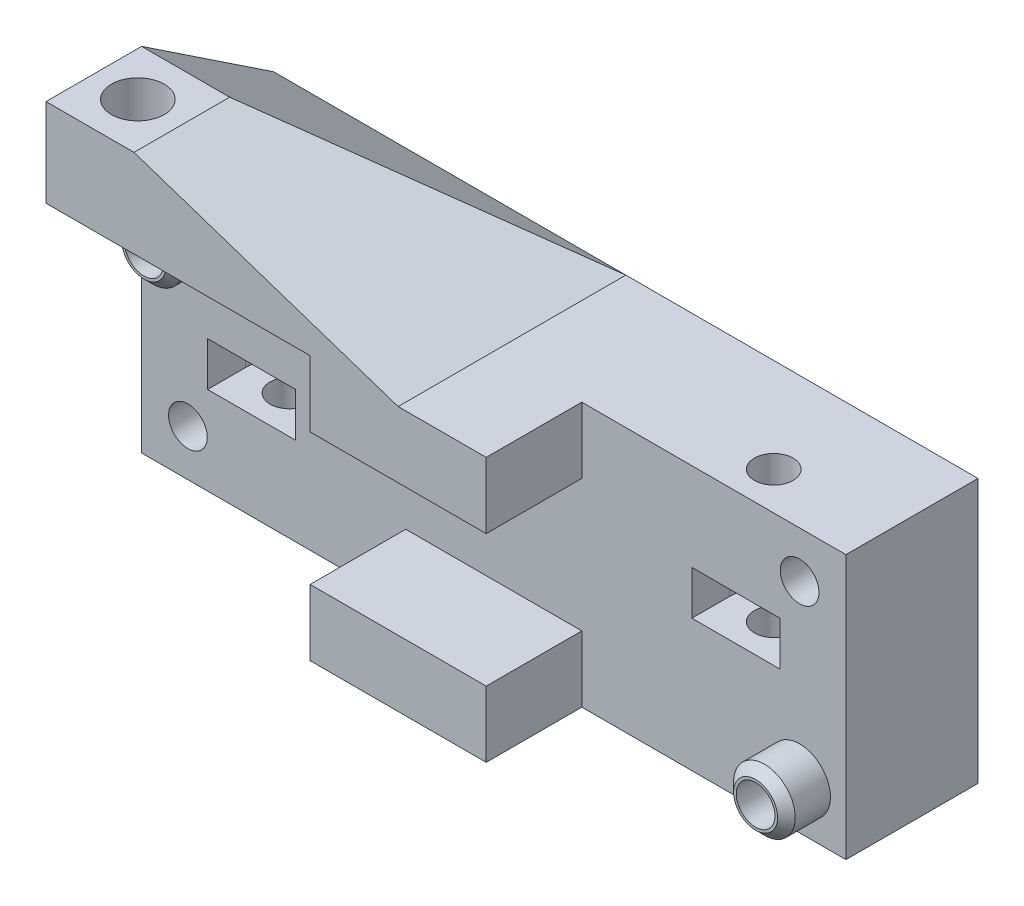
SolidWorks part; units mm, degrees
ref_plane "Front Plane" through (0, 0, 0) normal (0, 0, 1) x (1, 0, 0)
ref_plane "Top Plane" through (0, 0, 0) normal (0, 1, 0) x (1, 0, 0)
ref_plane "Right Plane" through (0, 0, 0) normal (1, 0, 0) x (0, 0, -1)
sketch "Sketch1" plane through (0, 0, 0) normal (0, 0, 1) x (1, 0, 0)
  line L1 (-25.4, 9.525) -> (25.4, 9.525)
  line L2 (-25.4, 9.525) -> (-25.4, -9.525)
  line L3 (-25.4, -9.525) -> (25.4, -9.525)
  line L4 (25.4, 9.525) -> (25.4, -9.525)
  line L5 (-25.4, 9.525) -> (25.4, -9.525) construction
  line L6 (-25.4, -9.525) -> (25.4, 9.525) construction
  point P0 (0, 0)
  dimension "D1" = 50.8
  dimension "D2" = 19.05
extrude "Boss-Extrude1" add sketch "Sketch1" along normal blind 9.525
sketch "Sketch11" plane through (0, 9.525, 0) normal (0, 1, 0) x (1, 0, 0)
  line L1 (-25.4, 0) -> (0, 0)
  line L2 (-25.4, 0) -> (-25.4, -16.4211)
  line L3 (-25.4, -16.4211) -> (0, -16.4211)
  line L4 (0, 0) -> (0, -16.4211)
  line L5 (-25.4, -25.9461) -> (-25.4, -16.4211) construction
  line L6 (12.6942, -16.4211) -> (0, -16.4211) construction
  dimension "D1" = 25.4
extrude "Boss-Extrude5" add sketch "Sketch11" along normal blind 6.35
sketch "Sketch2" plane through (0, 0, 9.525) normal (0, 0, 1) x (1, 0, 0)
  line L0 (-22.0599, -6.1849) -> (-22.0599, 6.1849) construction
  line L1 (-22.0599, 6.1849) -> (-25.4, 6.1849) construction
  line L2 (-25.4, 9.525) -> (-25.4, -9.525) construction
  line L3 (-22.0599, 6.1849) -> (-22.0599, 9.525) construction
  line L4 (25.4, 9.525) -> (0, 9.525) construction
  line L5 (0, -9.525) -> (0, 9.525) construction
  line L6 (25.4, 9.525) -> (0, 9.525) construction
  circle A0 centre (-22.0599, -6.1849) radius 1.397
  circle A1 centre (-22.0599, 6.1849) radius 1.397
  circle A2 centre (22.0599, -6.1849) radius 1.397
  circle A3 centre (22.0599, 6.1849) radius 1.397
  point P4 (-22.0599, 0)
  point P16 (0, 0)
  dimension "D1" = 2.794
  dimension "D2" = 2.794
  dimension "D3" = 12.3698
extrude "Cut-Extrude1" cut sketch "Sketch2" against normal through all
sketch "Sketch5" plane through (0, 9.525, 0) normal (0, 1, 0) x (1, 0, 0)
  line L0 (-25.4, -9.525) -> (-25.4, 0) construction
  line L1 (25.4, 0) -> (0, 0) construction
  line L2 (0, 0) -> (0, -9.525) construction
  line L4 (25.4, -9.525) -> (0, -9.525) construction
  circle A0 centre (-17.4625, -6.7945) radius 1.397
  circle A1 centre (17.4625, -6.7945) radius 1.397
  dimension "D1" = 7.9375
  dimension "D2" = 2.794
  dimension "D3" = 6.7945
extrude "Cut-Extrude3" cut sketch "Sketch5" against normal through all
sketch "Sketch3" plane through (0, 9.525, 0) normal (0, 1, 0) x (1, 0, 0)
  line L0 (-20.6375, -6.7945) -> (-20.6375, -9.525)
  line L1 (25.4, -9.525) -> (0, -9.525) construction
  line L2 (-14.2875, -6.7945) -> (-14.2875, -9.525)
  line L3 (-14.2875, -9.525) -> (-20.6375, -9.525)
  arc A0 (-14.2875, -6.7945) -> (-20.6375, -6.7945) centre (-17.4625, -6.7945) ccw
  circle A1 centre (-17.4625, -6.7945) radius 1.397 construction
  dimension "D1" = 3.175
extrude "Cut-Extrude2" cut sketch "Sketch3" against normal blind 3.175 from offset 9.525 offset against normal yes
sketch "Sketch6" plane through (0, 9.525, 0) normal (0, 1, 0) x (1, 0, 0)
  line L0 (14.2875, -6.7945) -> (14.2875, -9.525)
  line L1 (25.4, -9.525) -> (0, -9.525) construction
  line L2 (20.6375, -6.7945) -> (20.6375, -9.525)
  line L3 (14.2875, -9.525) -> (20.6375, -9.525)
  arc A0 (20.6375, -6.7945) -> (14.2875, -6.7945) centre (17.4625, -6.7945) ccw
  dimension "D1" = 6.35
extrude "Cut-Extrude4" cut sketch "Sketch6" against normal blind 3.175 from offset 6.35 offset against normal yes
sketch "Sketch7" plane through (0, 0, 9.525) normal (0, 0, 1) x (1, 0, 0)
  circle A0 centre (-22.0599, 6.1849) radius 2.2225
  circle A1 centre (-22.0599, 6.1849) radius 1.397
  circle A2 centre (22.0599, -6.1849) radius 2.2225
  circle A3 centre (22.0599, -6.1849) radius 1.397
  circle A5 centre (-22.0599, 6.1849) radius 1.397 construction
  circle A6 centre (22.0599, -6.1849) radius 1.397 construction
  dimension "D1" = 4.445
extrude "Boss-Extrude2" add sketch "Sketch7" along normal blind 3.175
chamfer "Chamfer1" distance 0.635 angle 45 2 edges at (-19.8374, 6.1849, 12.7) (24.2824, -6.1849, 12.7)
sketch "Sketch10" plane through (0, 0, 9.525) normal (0, 0, 1) x (1, 0, 0)
  line L0 (25.4, 9.525) -> (0, 9.525) construction
  line L1 (-6.35, 9.525) -> (6.35, 9.525)
  line L2 (-6.35, 9.525) -> (-6.35, 4.7625)
  line L3 (-6.35, 4.7625) -> (6.35, 4.7625)
  line L4 (6.35, 9.525) -> (6.35, 4.7625)
  line L5 (-25.4, -9.525) -> (25.4, -9.525) construction
  line L6 (-6.35, -9.525) -> (6.35, -9.525)
  line L7 (-6.35, -9.525) -> (-6.35, -4.7625)
  line L8 (-6.35, -4.7625) -> (6.35, -4.7625)
  line L9 (6.35, -9.525) -> (6.35, -4.7625)
  point P6 (0, 4.7625)
  point P14 (0, -4.7625)
  dimension "D1" = 12.7
  dimension "D2" = 4.7625
  dimension "D3" = 4.7625
  dimension "D4" = 12.7
extrude "Boss-Extrude4" add sketch "Sketch10" along normal blind 6.8961
chamfer "Chamfer2" distance 6.35 distance2 9.525 1 edges at (-12.7, 15.875, 0) first distance on face at (-20.6629, 6.1849, 0)
chamfer "Chamfer3" distance 6.35 distance2 19.05 1 edges at (0, 15.875, 12.9731) first distance on face at (0, 12.7, 10.5918)
sketch "Sketch12" plane through (0, 15.875, 0) normal (0, 1, 0) x (1, 0, 0)
  line L0 (-22.225, -12.9731) -> (-25.4, -12.9731) construction
  line L1 (-25.4, -9.525) -> (-25.4, -16.4211) construction
  line L2 (-22.225, -12.9731) -> (-19.05, -12.9731) construction
  line L3 (-19.05, -16.4211) -> (-19.05, -9.525) construction
  line L4 (-22.225, -9.525) -> (-22.225, -12.9731) construction
  line L5 (-19.05, -9.525) -> (-25.4, -9.525) construction
  line L6 (-22.225, -16.4211) -> (-22.225, -12.9731) construction
  line L7 (-25.4, -16.4211) -> (-19.05, -16.4211) construction
  circle A0 centre (-22.225, -12.9731) radius 1.905
  dimension "D1" = 3.81
extrude "Cut-Extrude5" cut sketch "Sketch12" against normal up to surface (6.35 mm away) up to face at (-15.875, 9.525, 12.9731)
